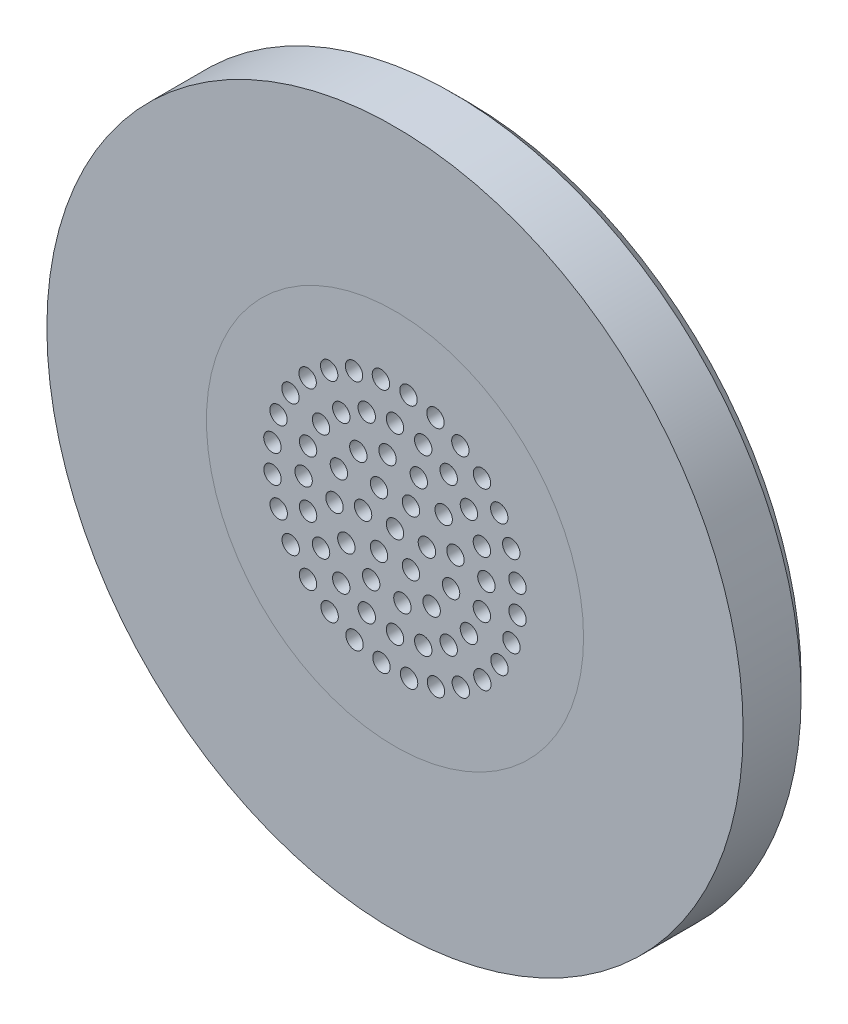
SolidWorks part; units mm, degrees
material "AISI 304"
ref_plane "Piano frontale" through (0, 0, 0) normal (0, 0, 1) x (1, 0, 0)
ref_plane "Piano superiore" through (0, 0, 0) normal (0, 1, 0) x (1, 0, 0)
ref_plane "Piano destro" through (0, 0, 0) normal (1, 0, 0) x (0, 0, -1)
sketch "Schizzo1" plane through (0, 0, 0) normal (0, 0, 1) x (1, 0, 0)
  line L0 (0, 0) -> (-24, 0) construction
  line L1 (0, 0) -> (-3.8661, 1.6411) construction
  line L2 (0, 0) -> (-8.4487, 0.9325) construction
  circle A0 centre (0, 0) radius 24
  circle A1 centre (-2.2, 0) radius 0.6
  circle A2 centre (0, 0) radius 2.2 construction
  circle A3 centre (0, 0) radius 4.2 construction
  circle A4 centre (0, 0) radius 0.6
  circle A5 centre (-3.8661, 1.6411) radius 0.6
  circle A6 centre (-1.1, 1.9053) radius 0.6
  circle A7 centre (1.1, 1.9053) radius 0.6
  circle A8 centre (2.2, 0) radius 0.6
  circle A9 centre (1.1, -1.9053) radius 0.6
  circle A10 centre (-1.1, -1.9053) radius 0.6
  circle A11 centre (-2.5276, 3.3543) radius 0.6
  circle A12 centre (-0.5119, 4.1687) radius 0.6
  circle A13 centre (1.6411, 3.8661) radius 0.6
  circle A14 centre (3.3543, 2.5276) radius 0.6
  circle A15 centre (4.1687, 0.5119) radius 0.6
  circle A16 centre (3.8661, -1.6411) radius 0.6
  circle A17 centre (2.5276, -3.3543) radius 0.6
  circle A18 centre (0.5119, -4.1687) radius 0.6
  circle A19 centre (-1.6411, -3.8661) radius 0.6
  circle A20 centre (-3.3543, -2.5276) radius 0.6
  circle A21 centre (-4.1687, -0.5119) radius 0.6
  circle A22 centre (0, 0) radius 6.3 construction
  circle A23 centre (-6.3, 0) radius 0.6
  circle A24 centre (-5.9917, 1.9468) radius 0.6
  circle A25 centre (-5.0968, 3.703) radius 0.6
  circle A26 centre (-3.703, 5.0968) radius 0.6
  circle A27 centre (-1.9468, 5.9917) radius 0.6
  circle A28 centre (0, 6.3) radius 0.6
  circle A29 centre (1.9468, 5.9917) radius 0.6
  circle A30 centre (3.703, 5.0968) radius 0.6
  circle A31 centre (5.0968, 3.703) radius 0.6
  circle A32 centre (5.9917, 1.9468) radius 0.6
  circle A33 centre (6.3, 0) radius 0.6
  circle A34 centre (5.9917, -1.9468) radius 0.6
  circle A35 centre (5.0968, -3.703) radius 0.6
  circle A36 centre (3.703, -5.0968) radius 0.6
  circle A37 centre (1.9468, -5.9917) radius 0.6
  circle A38 centre (0, -6.3) radius 0.6
  circle A39 centre (-1.9468, -5.9917) radius 0.6
  circle A40 centre (-3.703, -5.0968) radius 0.6
  circle A41 centre (-5.0968, -3.703) radius 0.6
  circle A42 centre (-5.9917, -1.9468) radius 0.6
  circle A43 centre (0, 0) radius 8.5 construction
  circle A44 centre (-8.4487, 0.9325) radius 0.6
  circle A45 centre (-8.0294, 2.7892) radius 0.6
  circle A46 centre (-7.2074, 4.5059) radius 0.6
  circle A47 centre (-6.024, 5.9968) radius 0.6
  circle A48 centre (-4.5386, 7.1869) radius 0.6
  circle A49 centre (-2.8256, 8.0166) radius 0.6
  circle A50 centre (-0.9708, 8.4444) radius 0.6
  circle A51 centre (0.9325, 8.4487) radius 0.6
  circle A52 centre (2.7892, 8.0294) radius 0.6
  circle A53 centre (4.5059, 7.2074) radius 0.6
  circle A54 centre (5.9968, 6.024) radius 0.6
  circle A55 centre (7.1869, 4.5386) radius 0.6
  circle A56 centre (8.0166, 2.8256) radius 0.6
  circle A57 centre (8.4444, 0.9708) radius 0.6
  circle A58 centre (8.4487, -0.9325) radius 0.6
  circle A59 centre (8.0294, -2.7892) radius 0.6
  circle A60 centre (7.2074, -4.5059) radius 0.6
  circle A61 centre (6.024, -5.9968) radius 0.6
  circle A62 centre (4.5386, -7.1869) radius 0.6
  circle A63 centre (2.8256, -8.0166) radius 0.6
  circle A64 centre (0.9708, -8.4444) radius 0.6
  circle A65 centre (-0.9325, -8.4487) radius 0.6
  circle A66 centre (-2.7892, -8.0294) radius 0.6
  circle A67 centre (-4.5059, -7.2074) radius 0.6
  circle A68 centre (-5.9968, -6.024) radius 0.6
  circle A69 centre (-7.1869, -4.5386) radius 0.6
  circle A70 centre (-8.0166, -2.8256) radius 0.6
  circle A71 centre (-8.4444, -0.9708) radius 0.6
  point P24 (0, 0)
  point P47 (0, 0)
  point P88 (0, 0)
  point P147 (0, 0)
  dimension "D1" = 1.2
  dimension "D3" = 4.4
  dimension "D4" = 8.4
  dimension "D5" = 6
  dimension "D7" = 12.6
  dimension "D10" = 17
  dimension "D11" = 48
  dimension "D2" = 23
  dimension "D6" = 12
  dimension "D8" = 20
  dimension "D9" = 28
extrude "Estrusione-Estrusione1" add sketch "Schizzo1" along normal blind 5
sketch "Schizzo4" plane through (0, 0, 5) normal (0, 0, 1) x (1, 0, 0)
  circle A0 centre (0, 0) radius 13
  dimension "D1" = 26
sketch "Schizzo5" plane through (0, 0, 0) normal (0, 0, -1) x (-1, 0, 0)
  circle A0 centre (0, 0) radius 13
  circle A1 centre (0, 0) radius 13 construction
split line "Linea di divisione1"
split line "Linea di divisione2"
chamfer "Smusso1" distance 1 angle 45 1 edges at (24, 0, 0)
chamfer "Smusso2" [suppressed] distance 1 angle 45
